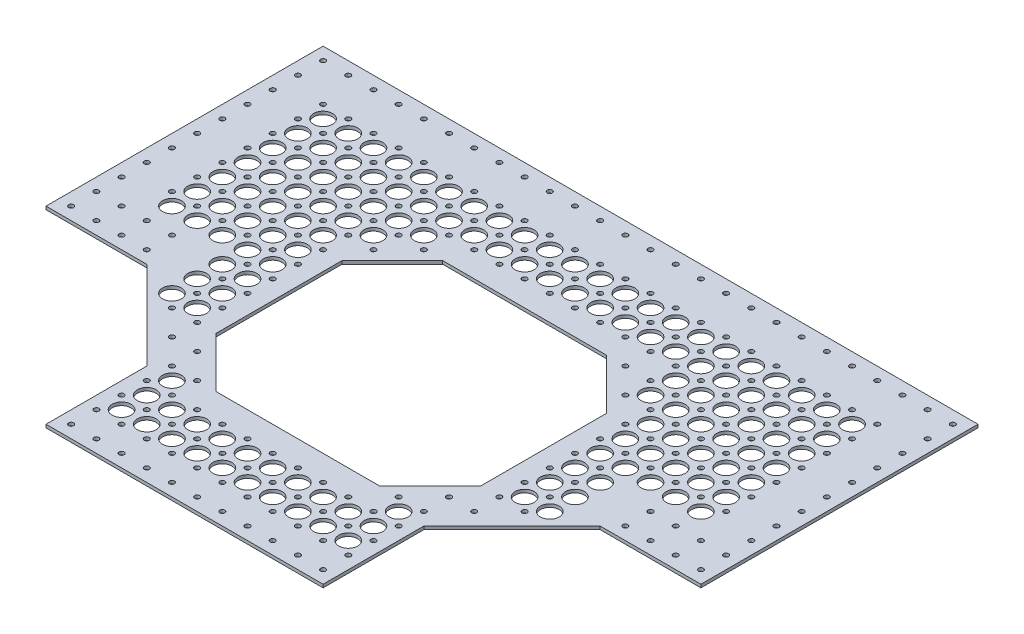
SolidWorks part; units mm, degrees
ref_plane "Front Plane" through (0, 0, 0) normal (0, 0, 1) x (1, 0, 0)
ref_plane "Top Plane" through (0, 0, 0) normal (0, 1, 0) x (1, 0, 0)
ref_plane "Right Plane" through (0, 0, 0) normal (1, 0, 0) x (0, 0, -1)
sketch "Sketch1" plane through (0, 0, 0) normal (0, 1, 0) x (1, 0, 0)
  line L0 (0, 0) -> (0, 101.6)
  line L1 (0, 101.6) -> (279.4, 101.6)
  line L2 (279.4, 101.6) -> (279.4, 0)
  line L3 (279.4, 0) -> (368.3045, -88.9045)
  line L4 (368.3045, -88.9045) -> (469.9045, -88.9045)
  line L5 (469.9045, -88.9045) -> (469.9045, -419.1045)
  line L6 (469.9045, -419.1045) -> (368.3045, -419.1045)
  line L7 (368.3045, -419.1045) -> (279.4, -508.0091)
  line L8 (279.4, -508.0091) -> (279.4, -609.6091)
  line L9 (279.4, -609.6091) -> (0, -609.6091)
  line L10 (0, -609.6091) -> (0, -508.0091)
  line L11 (0, -508.0091) -> (-88.9045, -419.1045)
  line L12 (-88.9045, -419.1045) -> (-190.5045, -419.1045)
  line L13 (-190.5045, -419.1045) -> (-190.5045, -88.9045)
  line L14 (-190.5045, -88.9045) -> (-88.9045, -88.9045)
  line L15 (-88.9045, -88.9045) -> (0, 0)
  line L16 (-190.5045, -88.9045) -> (-177.8045, -88.9045)
  line L17 (-177.8045, -88.9045) -> (-177.8045, -419.1045) construction
  line L18 (-177.8045, -419.1045) -> (-190.5045, -419.1045)
  line L19 (-177.8045, -101.6045) -> (-177.8045, -127.0045) construction
  line L20 (139.7, -898.4) -> (139.7, 49101.6) construction
  line L21 (-966.4523, 88.9) -> (49033.5477, 88.9) construction
  line L22 (12.7, 88.9) -> (38.1, 88.9) construction
  line L23 (-1190.5045, -254.0045) -> (48809.4955, -254.0045) construction
  line L24 (-190.5045, -368.3045) -> (-88.9045, -368.3045) construction
  line L25 (-88.9045, -368.3045) -> (-88.9045, -419.1045) construction
  line L26 (-101.6045, -406.4045) -> (-127.0045, -406.4045) construction
  line L27 (-101.6045, -381.0045) -> (-127.0045, -381.0045) construction
  line L28 (-1102.5698, -114.3045) -> (48897.4302, -114.3045) construction
  line L29 (-1089.6596, -165.1045) -> (48910.3404, -165.1045) construction
  line L30 (-177.8045, -127.0045) -> (-152.4045, -127.0045) construction
  circle A0 centre (-177.8045, -101.6045) radius 2.54
  circle A1 centre (-177.8045, -127.0045) radius 2.54
  circle A2 centre (-177.8045, -152.4045) radius 2.54
  circle A3 centre (-177.8045, -177.8045) radius 2.54
  circle A4 centre (-177.8045, -203.2045) radius 2.54
  circle A5 centre (-177.8045, -228.6045) radius 2.54
  circle A6 centre (-177.8045, -254.0045) radius 2.54
  circle A7 centre (-177.8045, -279.4045) radius 2.54
  circle A8 centre (-177.8045, -304.8045) radius 2.54
  circle A9 centre (-177.8045, -330.2045) radius 2.54
  circle A10 centre (-177.8045, -355.6045) radius 2.54
  circle A11 centre (-177.8045, -381.0045) radius 2.54
  circle A12 centre (-177.8045, -406.4045) radius 2.54
  circle A13 centre (457.2045, -406.4045) radius 2.54
  circle A14 centre (457.2045, -381.0045) radius 2.54
  circle A15 centre (457.2045, -355.6045) radius 2.54
  circle A16 centre (457.2045, -330.2045) radius 2.54
  circle A17 centre (457.2045, -304.8045) radius 2.54
  circle A18 centre (457.2045, -279.4045) radius 2.54
  circle A19 centre (457.2045, -254.0045) radius 2.54
  circle A20 centre (457.2045, -228.6045) radius 2.54
  circle A21 centre (457.2045, -152.4045) radius 2.54
  circle A22 centre (457.2045, -177.8045) radius 2.54
  circle A23 centre (457.2045, -203.2045) radius 2.54
  circle A24 centre (457.2045, -127.0045) radius 2.54
  circle A25 centre (457.2045, -101.6045) radius 2.54
  circle A26 centre (12.7, 88.9) radius 2.54
  circle A27 centre (38.1, 88.9) radius 2.54
  circle A28 centre (63.5, 88.9) radius 2.54
  circle A29 centre (88.9, 88.9) radius 2.54
  circle A30 centre (114.3, 88.9) radius 2.54
  circle A31 centre (139.7, 88.9) radius 2.54
  circle A32 centre (165.1, 88.9) radius 2.54
  circle A33 centre (190.5, 88.9) radius 2.54
  circle A34 centre (215.9, 88.9) radius 2.54
  circle A35 centre (241.3, 88.9) radius 2.54
  circle A36 centre (266.7, 88.9) radius 2.54
  circle A37 centre (266.7, -596.9091) radius 2.54
  circle A38 centre (241.3, -596.9091) radius 2.54
  circle A39 centre (215.9, -596.9091) radius 2.54
  circle A40 centre (190.5, -596.9091) radius 2.54
  circle A41 centre (165.1, -596.9091) radius 2.54
  circle A42 centre (139.7, -596.9091) radius 2.54
  circle A43 centre (114.3, -596.9091) radius 2.54
  circle A44 centre (88.9, -596.9091) radius 2.54
  circle A45 centre (63.5, -596.9091) radius 2.54
  circle A46 centre (38.1, -596.9091) radius 2.54
  circle A47 centre (12.7, -596.9091) radius 2.54
  circle A48 centre (-101.6045, -381.0045) radius 2.54
  circle A49 centre (-101.6045, -406.4045) radius 2.54
  circle A50 centre (381.0045, -406.4045) radius 2.54
  circle A51 centre (381.0045, -381.0045) radius 2.54
  circle A52 centre (-127.0045, -406.4045) radius 2.54
  circle A53 centre (-152.4045, -406.4045) radius 2.54
  circle A54 centre (-127.0045, -381.0045) radius 2.54
  circle A55 centre (-152.4045, -381.0045) radius 2.54
  circle A56 centre (431.8045, -381.0045) radius 2.54
  circle A57 centre (406.4045, -381.0045) radius 2.54
  circle A58 centre (431.8045, -406.4045) radius 2.54
  circle A59 centre (406.4045, -406.4045) radius 2.54
  circle A60 centre (-152.4045, -127.0045) radius 2.54
  circle A61 centre (-152.4045, -152.4045) radius 2.54
  circle A62 centre (-127.0045, -127.0045) radius 2.54
  circle A63 centre (-127.0045, -152.4045) radius 2.54
  circle A64 centre (-101.6045, -127.0045) radius 2.54
  circle A65 centre (-101.6045, -152.4045) radius 2.54
  circle A66 centre (-76.2045, -127.0045) radius 2.54
  circle A67 centre (-76.2045, -152.4045) radius 2.54
  circle A68 centre (-50.8045, -127.0045) radius 2.54
  circle A69 centre (-50.8045, -152.4045) radius 2.54
  circle A70 centre (-25.4045, -127.0045) radius 2.54
  circle A71 centre (-25.4045, -152.4045) radius 2.54
  circle A72 centre (-0.0045, -127.0045) radius 2.54
  circle A73 centre (-0.0045, -152.4045) radius 2.54
  circle A74 centre (25.3955, -127.0045) radius 2.54
  circle A75 centre (25.3955, -152.4045) radius 2.54
  circle A76 centre (50.7955, -127.0045) radius 2.54
  circle A77 centre (50.7955, -152.4045) radius 2.54
  circle A78 centre (76.1955, -127.0045) radius 2.54
  circle A79 centre (76.1955, -152.4045) radius 2.54
  circle A80 centre (101.5955, -127.0045) radius 2.54
  circle A81 centre (101.5955, -152.4045) radius 2.54
  circle A82 centre (126.9955, -127.0045) radius 2.54
  circle A83 centre (126.9955, -152.4045) radius 2.54
  circle A84 centre (152.3955, -127.0045) radius 2.54
  circle A85 centre (152.3955, -152.4045) radius 2.54
  circle A86 centre (177.7955, -127.0045) radius 2.54
  circle A87 centre (177.7955, -152.4045) radius 2.54
  circle A88 centre (203.1955, -127.0045) radius 2.54
  circle A89 centre (203.1955, -152.4045) radius 2.54
  circle A90 centre (228.5955, -127.0045) radius 2.54
  circle A91 centre (228.5955, -152.4045) radius 2.54
  circle A92 centre (253.9955, -127.0045) radius 2.54
  circle A93 centre (253.9955, -152.4045) radius 2.54
  circle A94 centre (279.3955, -127.0045) radius 2.54
  circle A95 centre (279.3955, -152.4045) radius 2.54
  circle A96 centre (304.7955, -127.0045) radius 2.54
  circle A97 centre (304.7955, -152.4045) radius 2.54
  circle A98 centre (330.1955, -127.0045) radius 2.54
  circle A99 centre (330.1955, -152.4045) radius 2.54
  circle A100 centre (355.5955, -127.0045) radius 2.54
  circle A101 centre (355.5955, -152.4045) radius 2.54
  circle A102 centre (380.9955, -127.0045) radius 2.54
  circle A103 centre (380.9955, -152.4045) radius 2.54
  circle A104 centre (406.3955, -127.0045) radius 2.54
  circle A105 centre (406.3955, -152.4045) radius 2.54
  circle A106 centre (431.7955, -127.0045) radius 2.54
  circle A107 centre (431.7955, -152.4045) radius 2.54
  point P50 (139.7, 101.6)
  point P105 (-190.5045, -254.0045)
  dimension "D11" = 5.08
  dimension "D16" = 5.08
  dimension "D21" = 5.08
  dimension "D22" = 5.08
  dimension "D1" = 135
  dimension "D2" = 135
  dimension "D3" = 135
  dimension "D4" = 135
  dimension "D5" = 101.6
  dimension "D6" = 279.4
  dimension "D7" = 330.2
  dimension "D8" = 101.6
  dimension "D9" = 125.73
  dimension "D10" = 12.7
  dimension "D12" = 12.7
  dimension "D13" = 25.4
  dimension "D15" = 12.7
  dimension "D17" = 12.7
  dimension "D18" = 25.4
  dimension "D19" = 101.6
  dimension "D20" = 50.8
  dimension "D23" = 12.7
  dimension "D24" = 12.7
  dimension "D25" = 12.7
  dimension "D26" = 12.7
  dimension "D27" = 25.4
  dimension "D28" = 25.4
  dimension "D29" = 25.4
  dimension "D30" = 50.8
  dimension "D31" = 25.4
  dimension "D14" = 13
extrude "Boss-Extrude1" add sketch "Sketch1" along normal blind 3.175 contours L15 L14 L13 L12 L11 L10 L9 L8 L7 L6 L5 L4 L3 L2 L1 L0 A107 A106 A105 A104 A103 A102 A101 A100 A99 A98 A97 A96 A95 A94 A93 A92 region at (139.7, 0, 254.2329)
sketch "Sketch2" plane through (0, 0, -101.6) normal (0, 0, -1) x (-1, 0, 0)
  line L1 (-510.5355, -12.7) -> (251.4645, -12.7)
  line L2 (-510.5355, -12.7) -> (-510.5355, 12.7)
  line L3 (-510.5355, 12.7) -> (251.4645, 12.7)
  line L4 (251.4645, -12.7) -> (251.4645, 12.7)
  line L5 (-510.5355, -12.7) -> (251.4645, 12.7) construction
  line L6 (-510.5355, 12.7) -> (251.4645, -12.7) construction
  point P0 (-129.5355, 0)
  dimension "D1" = 762
  dimension "D2" = 25.4
extrude "Cut-Extrude1" cut sketch "Sketch2" against normal blind 241.3
sketch "Sketch3" plane through (0, 3.175, 0) normal (0, 1, 0) x (1, 0, 0)
  line L0 (-990.1544, -317.5045) -> (49009.8456, -317.5045) construction
  line L1 (-88.9045, -419.1045) -> (-190.5045, -419.1045) construction
  line L2 (-925.1076, -514.3545) -> (49074.8924, -514.3545) construction
  line L3 (139.7, 330.1887) -> (139.7, -609.6091) construction
  line L12 (6.35, -495.3045) -> (273.05, -495.3045)
  line L13 (279.4, -609.6091) -> (0, -609.6091) construction
  line L14 (0, -609.6091) -> (0, -508.0091) construction
  line L15 (6.35, -495.3045) -> (6.35, -317.5045)
  line L16 (6.35, -317.5045) -> (273.05, -317.5045)
  line L17 (273.05, -495.3045) -> (273.05, -317.5045)
  line L18 (6.35, -495.3045) -> (273.05, -317.5045) construction
  line L19 (6.35, -317.5045) -> (273.05, -495.3045) construction
  point P5 (139.7, -406.4045)
  point P9 (139.7, -139.7102)
  point P19 (139.7, -139.7102)
  dimension "D1" = 101.6
  dimension "D2" = 95.25
  dimension "D3" = 177.8
  dimension "D4" = 266.7
  dimension "D6" = 139.7
extrude "Cut-Extrude2" cut sketch "Sketch3" against normal blind 3.175
sketch "Sketch4" plane through (0, 3.175, 0) normal (0, 1, 0) x (1, 0, 0)
  line L0 (222.25, -495.3045) -> (273.05, -444.5045)
  line L1 (6.35, -495.3045) -> (273.05, -495.3045) construction
  line L2 (273.05, -495.3045) -> (273.05, -317.5045) construction
  line L3 (222.25, -495.3045) -> (273.05, -495.3045)
  line L4 (273.05, -495.3045) -> (273.05, -444.5045)
  line L5 (139.7, 369.2915) -> (139.7, -648.6915) construction
  line L7 (279.4, -508.0091) -> (279.4, -609.6091) construction
  line L8 (6.35, -495.3045) -> (6.35, -444.5045)
  line L9 (57.15, -495.3045) -> (6.35, -495.3045)
  line L10 (57.15, -495.3045) -> (6.35, -444.5045)
  point P10 (139.7, -139.7)
  dimension "D1" = 135
  dimension "D2" = 50.8
  dimension "D3" = 139.7
extrude "Boss-Extrude2" add sketch "Sketch4" against normal blind 3.175
sketch "Sketch7" plane through (0, 3.175, 0) normal (0, 1, 0) x (1, 0, 0)
  line L0 (6.35, -317.5045) -> (57.15, -266.7045)
  line L1 (57.15, -266.7045) -> (222.25, -266.7045)
  line L2 (222.25, -266.7045) -> (273.05, -317.5045)
  line L3 (273.05, -317.5045) -> (6.35, -317.5045) construction
  line L4 (6.35, -317.5045) -> (273.05, -317.5045)
  dimension "D1" = 165.1
  dimension "D2" = 45
  dimension "D3" = 45
extrude "Cut-Extrude3" cut sketch "Sketch7" against normal blind 3.175
sketch "Sketch8" plane through (0, 3.175, 0) normal (0, 1, 0) x (1, 0, 0)
  line L0 (-88.9045, -419.1045) -> (-190.5045, -419.1045) construction
  line L1 (0, -609.6091) -> (0, -508.0091) construction
  line L2 (12.7, -596.9091) -> (12.7, -571.5091) construction
  line L3 (279.4, -508.0091) -> (279.4, -609.6091) construction
  line L4 (76.1955, -533.4) -> (101.5955, -533.4) construction
  line L5 (292.1, -292.1091) -> (292.1, -317.5091) construction
  line L6 (-190.5045, -419.1045) -> (-190.5045, -139.7) construction
  line L7 (-190.5045, -139.7) -> (469.9045, -139.7) construction
  line L8 (-127.0045, -203.2) -> (-101.6045, -203.2) construction
  line L9 (-127.0045, -203.2) -> (-127.0045, -228.6) construction
  line L10 (-25.4045, -381) -> (-50.8045, -381) construction
  line L11 (50.7955, -533.4) -> (25.3955, -533.4) construction
  line L12 (228.5955, -533.4) -> (253.9955, -533.4) construction
  line L13 (25.3955, -533.4) -> (25.3955, -508) construction
  line L14 (253.9955, -533.4) -> (253.9955, -508) construction
  line L15 (330.1955, -431.8) -> (304.7955, -431.8) construction
  line L16 (304.7955, -279.4) -> (279.3955, -279.4) construction
  circle A0 centre (12.7, -596.9091) radius 2.54
  circle A1 centre (12.7, -571.5091) radius 2.54
  circle A2 centre (12.7, -546.1091) radius 2.54
  circle A3 centre (12.7, -520.7091) radius 2.54
  circle A4 centre (12.7, -495.3091) radius 2.54
  circle A5 centre (12.7, -469.9091) radius 2.54
  circle A12 centre (12.7, -292.1091) radius 2.54
  circle A13 centre (12.7, -266.7091) radius 2.54
  circle A14 centre (12.7, -241.3091) radius 2.54
  circle A15 centre (12.7, -215.9091) radius 2.54
  circle A16 centre (12.7, -190.5091) radius 2.54
  circle A19 centre (38.1, -190.5091) radius 2.54
  circle A20 centre (38.1, -215.9091) radius 2.54
  circle A21 centre (38.1, -241.3091) radius 2.54
  circle A22 centre (38.1, -266.7091) radius 2.54
  circle A30 centre (38.1, -495.3091) radius 2.54
  circle A31 centre (38.1, -520.7091) radius 2.54
  circle A32 centre (38.1, -546.1091) radius 2.54
  circle A33 centre (38.1, -571.5091) radius 2.54
  circle A35 centre (63.5, -190.5091) radius 2.54
  circle A36 centre (63.5, -215.9091) radius 2.54
  circle A37 centre (63.5, -241.3091) radius 2.54
  circle A47 centre (63.5, -520.7091) radius 2.54
  circle A48 centre (63.5, -546.1091) radius 2.54
  circle A49 centre (63.5, -571.5091) radius 2.54
  circle A51 centre (88.9, -190.5091) radius 2.54
  circle A52 centre (88.9, -215.9091) radius 2.54
  circle A53 centre (88.9, -241.3091) radius 2.54
  circle A63 centre (88.9, -520.7091) radius 2.54
  circle A64 centre (88.9, -546.1091) radius 2.54
  circle A65 centre (88.9, -571.5091) radius 2.54
  circle A67 centre (114.3, -190.5091) radius 2.54
  circle A68 centre (114.3, -215.9091) radius 2.54
  circle A69 centre (114.3, -241.3091) radius 2.54
  circle A79 centre (114.3, -520.7091) radius 2.54
  circle A80 centre (114.3, -546.1091) radius 2.54
  circle A81 centre (114.3, -571.5091) radius 2.54
  circle A83 centre (139.7, -190.5091) radius 2.54
  circle A84 centre (139.7, -215.9091) radius 2.54
  circle A85 centre (139.7, -241.3091) radius 2.54
  circle A95 centre (139.7, -520.7091) radius 2.54
  circle A96 centre (139.7, -546.1091) radius 2.54
  circle A97 centre (139.7, -571.5091) radius 2.54
  circle A99 centre (165.1, -190.5091) radius 2.54
  circle A100 centre (165.1, -215.9091) radius 2.54
  circle A101 centre (165.1, -241.3091) radius 2.54
  circle A111 centre (165.1, -520.7091) radius 2.54
  circle A112 centre (165.1, -546.1091) radius 2.54
  circle A113 centre (165.1, -571.5091) radius 2.54
  circle A115 centre (190.5, -190.5091) radius 2.54
  circle A116 centre (190.5, -215.9091) radius 2.54
  circle A117 centre (190.5, -241.3091) radius 2.54
  circle A127 centre (190.5, -520.7091) radius 2.54
  circle A128 centre (190.5, -546.1091) radius 2.54
  circle A129 centre (190.5, -571.5091) radius 2.54
  circle A131 centre (215.9, -190.5091) radius 2.54
  circle A132 centre (215.9, -215.9091) radius 2.54
  circle A133 centre (215.9, -241.3091) radius 2.54
  circle A143 centre (215.9, -520.7091) radius 2.54
  circle A144 centre (215.9, -546.1091) radius 2.54
  circle A145 centre (215.9, -571.5091) radius 2.54
  circle A147 centre (241.3, -190.5091) radius 2.54
  circle A148 centre (241.3, -215.9091) radius 2.54
  circle A149 centre (241.3, -241.3091) radius 2.54
  circle A150 centre (241.3, -266.7091) radius 2.54
  circle A158 centre (241.3, -495.3091) radius 2.54
  circle A159 centre (241.3, -520.7091) radius 2.54
  circle A160 centre (241.3, -546.1091) radius 2.54
  circle A161 centre (241.3, -571.5091) radius 2.54
  circle A163 centre (266.7, -190.5091) radius 2.54
  circle A164 centre (266.7, -215.9091) radius 2.54
  circle A165 centre (266.7, -241.3091) radius 2.54
  circle A166 centre (266.7, -266.7091) radius 2.54
  circle A167 centre (266.7, -292.1091) radius 2.54
  circle A173 centre (266.7, -469.9091) radius 2.54
  circle A174 centre (266.7, -495.3091) radius 2.54
  circle A175 centre (266.7, -520.7091) radius 2.54
  circle A176 centre (266.7, -546.1091) radius 2.54
  circle A177 centre (266.7, -571.5091) radius 2.54
  circle A179 centre (292.1, -190.5091) radius 2.54
  circle A180 centre (292.1, -215.9091) radius 2.54
  circle A181 centre (292.1, -241.3091) radius 2.54
  circle A182 centre (292.1, -266.7091) radius 2.54
  circle A183 centre (292.1, -292.1091) radius 2.54
  circle A189 centre (292.1, -469.9091) radius 2.54
  circle A195 centre (317.5, -190.5091) radius 2.54
  circle A196 centre (317.5, -215.9091) radius 2.54
  circle A197 centre (317.5, -241.3091) radius 2.54
  circle A198 centre (317.5, -266.7091) radius 2.54
  circle A199 centre (317.5, -292.1091) radius 2.54
  circle A211 centre (342.9, -190.5091) radius 2.54
  circle A212 centre (342.9, -215.9091) radius 2.54
  circle A213 centre (342.9, -241.3091) radius 2.54
  circle A214 centre (342.9, -266.7091) radius 2.54
  circle A215 centre (342.9, -292.1091) radius 2.54
  circle A227 centre (368.3, -190.5091) radius 2.54
  circle A228 centre (368.3, -215.9091) radius 2.54
  circle A229 centre (368.3, -241.3091) radius 2.54
  circle A230 centre (368.3, -266.7091) radius 2.54
  circle A231 centre (368.3, -292.1091) radius 2.54
  circle A243 centre (393.7, -190.5091) radius 2.54
  circle A244 centre (393.7, -215.9091) radius 2.54
  circle A245 centre (393.7, -241.3091) radius 2.54
  circle A246 centre (393.7, -266.7091) radius 2.54
  circle A247 centre (393.7, -292.1091) radius 2.54
  circle A259 centre (419.1, -190.5091) radius 2.54
  circle A260 centre (419.1, -215.9091) radius 2.54
  circle A261 centre (419.1, -241.3091) radius 2.54
  circle A262 centre (419.1, -266.7091) radius 2.54
  circle A263 centre (419.1, -292.1091) radius 2.54
  circle A291 centre (-12.7, -190.5091) radius 2.54
  circle A292 centre (-12.7, -215.9091) radius 2.54
  circle A293 centre (-12.7, -241.3091) radius 2.54
  circle A294 centre (-12.7, -266.7091) radius 2.54
  circle A295 centre (-12.7, -292.1091) radius 2.54
  circle A302 centre (-12.7, -469.9091) radius 2.54
  circle A308 centre (-38.1, -190.5091) radius 2.54
  circle A309 centre (-38.1, -215.9091) radius 2.54
  circle A310 centre (-38.1, -241.3091) radius 2.54
  circle A311 centre (-38.1, -266.7091) radius 2.54
  circle A312 centre (-38.1, -292.1091) radius 2.54
  circle A325 centre (-63.5, -190.5091) radius 2.54
  circle A326 centre (-63.5, -215.9091) radius 2.54
  circle A327 centre (-63.5, -241.3091) radius 2.54
  circle A328 centre (-63.5, -266.7091) radius 2.54
  circle A329 centre (-63.5, -292.1091) radius 2.54
  circle A342 centre (-88.9, -190.5091) radius 2.54
  circle A343 centre (-88.9, -215.9091) radius 2.54
  circle A344 centre (-88.9, -241.3091) radius 2.54
  circle A345 centre (-88.9, -266.7091) radius 2.54
  circle A346 centre (-88.9, -292.1091) radius 2.54
  circle A359 centre (-114.3, -190.5091) radius 2.54
  circle A360 centre (-114.3, -215.9091) radius 2.54
  circle A361 centre (-114.3, -241.3091) radius 2.54
  circle A362 centre (-114.3, -266.7091) radius 2.54
  circle A363 centre (-114.3, -292.1091) radius 2.54
  circle A376 centre (-139.7, -190.5091) radius 2.54
  circle A377 centre (-139.7, -215.9091) radius 2.54
  circle A378 centre (-139.7, -241.3091) radius 2.54
  circle A379 centre (-139.7, -266.7091) radius 2.54
  circle A380 centre (-139.7, -292.1091) radius 2.54
  circle A409 centre (-63.5, -495.3091) radius 2.54 [skipped]
  circle A410 centre (-63.5, -520.7091) radius 2.54 [skipped]
  circle A411 centre (-63.5, -546.1091) radius 2.54 [skipped]
  circle A412 centre (-63.5, -571.5091) radius 2.54 [skipped]
  circle A413 centre (-88.9, -469.9091) radius 2.54 [skipped]
  circle A414 centre (-88.9, -495.3091) radius 2.54 [skipped]
  circle A415 centre (-88.9, -520.7091) radius 2.54 [skipped]
  circle A416 centre (-88.9, -546.1091) radius 2.54 [skipped]
  circle A417 centre (-88.9, -571.5091) radius 2.54 [skipped]
  circle A418 centre (-114.3, -469.9091) radius 2.54 [skipped]
  circle A419 centre (-114.3, -495.3091) radius 2.54 [skipped]
  circle A420 centre (-114.3, -520.7091) radius 2.54 [skipped]
  circle A421 centre (-114.3, -546.1091) radius 2.54 [skipped]
  circle A422 centre (-114.3, -571.5091) radius 2.54 [skipped]
  circle A423 centre (-139.7, -469.9091) radius 2.54 [skipped]
  circle A424 centre (-139.7, -495.3091) radius 2.54 [skipped]
  circle A425 centre (-139.7, -520.7091) radius 2.54 [skipped]
  circle A426 centre (-139.7, -546.1091) radius 2.54 [skipped]
  circle A427 centre (-139.7, -571.5091) radius 2.54 [skipped]
  circle A428 centre (-165.1, -469.9091) radius 2.54 [skipped]
  circle A429 centre (-165.1, -495.3091) radius 2.54 [skipped]
  circle A430 centre (-165.1, -520.7091) radius 2.54 [skipped]
  circle A431 centre (-165.1, -546.1091) radius 2.54 [skipped]
  circle A432 centre (-165.1, -571.5091) radius 2.54 [skipped]
  circle A433 centre (-63.5, -469.9091) radius 2.54 [skipped]
  circle A434 centre (-12.7, -495.3091) radius 2.54 [skipped]
  circle A435 centre (-12.7, -520.7091) radius 2.54 [skipped]
  circle A436 centre (-12.7, -546.1091) radius 2.54 [skipped]
  circle A437 centre (-12.7, -571.5091) radius 2.54 [skipped]
  circle A438 centre (-38.1, -495.3091) radius 2.54 [skipped]
  circle A439 centre (-38.1, -520.7091) radius 2.54 [skipped]
  circle A440 centre (-38.1, -546.1091) radius 2.54 [skipped]
  circle A441 centre (-38.1, -571.5091) radius 2.54 [skipped]
  circle A442 centre (-127.0045, -203.2) radius 9.525
  circle A443 centre (-101.6045, -203.2) radius 9.525
  circle A444 centre (-76.2045, -203.2) radius 9.525
  circle A445 centre (-50.8045, -203.2) radius 9.525
  circle A446 centre (-25.4045, -203.2) radius 9.525
  circle A447 centre (-0.0045, -203.2) radius 9.525
  circle A448 centre (25.3955, -203.2) radius 9.525
  circle A449 centre (50.7955, -203.2) radius 9.525
  circle A450 centre (76.1955, -203.2) radius 9.525
  circle A451 centre (-38.1, -469.9091) radius 2.54 [skipped]
  circle A452 centre (101.5955, -203.2) radius 9.525
  circle A453 centre (126.9955, -203.2) radius 9.525
  circle A454 centre (152.3955, -203.2) radius 9.525
  circle A455 centre (177.7955, -203.2) radius 9.525
  circle A456 centre (203.1955, -203.2) radius 9.525
  circle A457 centre (228.5955, -203.2) radius 9.525
  circle A458 centre (253.9955, -203.2) radius 9.525
  circle A459 centre (279.3955, -203.2) radius 9.525
  circle A460 centre (304.7955, -203.2) radius 9.525
  circle A461 centre (330.1955, -203.2) radius 9.525
  circle A462 centre (355.5955, -203.2) radius 9.525
  circle A463 centre (380.9955, -203.2) radius 9.525
  circle A464 centre (406.3955, -203.2) radius 9.525
  circle A467 centre (-101.6045, -228.6) radius 9.525
  circle A468 centre (-76.2045, -228.6) radius 9.525
  circle A469 centre (-50.8045, -228.6) radius 9.525
  circle A470 centre (-25.4045, -228.6) radius 9.525
  circle A471 centre (-0.0045, -228.6) radius 9.525
  circle A472 centre (25.3955, -228.6) radius 9.525
  circle A473 centre (50.7955, -228.6) radius 9.525
  circle A474 centre (76.1955, -228.6) radius 9.525
  circle A475 centre (101.5955, -228.6) radius 9.525
  circle A476 centre (126.9955, -228.6) radius 9.525
  circle A477 centre (152.3955, -228.6) radius 9.525
  circle A478 centre (177.7955, -228.6) radius 9.525
  circle A479 centre (203.1955, -228.6) radius 9.525
  circle A480 centre (228.5955, -228.6) radius 9.525
  circle A481 centre (253.9955, -228.6) radius 9.525
  circle A482 centre (279.3955, -228.6) radius 9.525
  circle A483 centre (304.7955, -228.6) radius 9.525
  circle A484 centre (330.1955, -228.6) radius 9.525
  circle A485 centre (355.5955, -228.6) radius 9.525
  circle A486 centre (380.9955, -228.6) radius 9.525
  circle A487 centre (406.3955, -228.6) radius 9.525
  circle A490 centre (-101.6045, -254) radius 9.525
  circle A491 centre (-76.2045, -254) radius 9.525
  circle A492 centre (-50.8045, -254) radius 9.525
  circle A493 centre (-25.4045, -254) radius 9.525
  circle A494 centre (-0.0045, -254) radius 9.525
  circle A495 centre (25.3955, -254) radius 9.525
  circle A497 centre (38.1, -292.1091) radius 2.54 [skipped]
  circle A498 centre (63.5, -292.1091) radius 2.54 [skipped]
  circle A499 centre (88.9, -292.1091) radius 2.54 [skipped]
  circle A500 centre (114.3, -292.1091) radius 2.54 [skipped]
  circle A501 centre (139.7, -292.1091) radius 2.54 [skipped]
  circle A502 centre (165.1, -292.1091) radius 2.54 [skipped]
  circle A503 centre (190.5, -292.1091) radius 2.54 [skipped]
  circle A504 centre (241.3, -292.1091) radius 2.54 [skipped]
  circle A505 centre (215.9, -292.1091) radius 2.54 [skipped]
  circle A506 centre (63.5, -266.7091) radius 2.54 [skipped]
  circle A507 centre (88.9, -266.7091) radius 2.54 [skipped]
  circle A508 centre (114.3, -266.7091) radius 2.54 [skipped]
  circle A509 centre (139.7, -266.7091) radius 2.54 [skipped]
  circle A510 centre (165.1, -266.7091) radius 2.54 [skipped]
  circle A511 centre (215.9, -266.7091) radius 2.54 [skipped]
  circle A512 centre (190.5, -266.7091) radius 2.54 [skipped]
  circle A518 centre (12.7, -419.1091) radius 2.54 [skipped]
  circle A519 centre (12.7, -393.7091) radius 2.54 [skipped]
  circle A520 centre (12.7, -368.3091) radius 2.54 [skipped]
  circle A521 centre (12.7, -342.9091) radius 2.54 [skipped]
  circle A522 centre (12.7, -317.5091) radius 2.54 [skipped]
  circle A523 centre (12.7, -444.5091) radius 2.54 [skipped]
  circle A524 centre (292.1, -546.1091) radius 2.54 [skipped]
  circle A525 centre (292.1, -571.5091) radius 2.54 [skipped]
  circle A526 centre (317.5, -520.7091) radius 2.54 [skipped]
  circle A527 centre (317.5, -546.1091) radius 2.54 [skipped]
  circle A528 centre (317.5, -571.5091) radius 2.54 [skipped]
  circle A529 centre (342.9, -520.7091) radius 2.54 [skipped]
  circle A530 centre (342.9, -546.1091) radius 2.54 [skipped]
  circle A531 centre (342.9, -571.5091) radius 2.54 [skipped]
  circle A532 centre (368.3, -520.7091) radius 2.54 [skipped]
  circle A533 centre (368.3, -546.1091) radius 2.54 [skipped]
  circle A534 centre (368.3, -571.5091) radius 2.54 [skipped]
  circle A535 centre (393.7, -520.7091) radius 2.54 [skipped]
  circle A536 centre (393.7, -546.1091) radius 2.54 [skipped]
  circle A537 centre (393.7, -571.5091) radius 2.54 [skipped]
  circle A538 centre (419.1, -520.7091) radius 2.54 [skipped]
  circle A539 centre (419.1, -546.1091) radius 2.54 [skipped]
  circle A540 centre (419.1, -571.5091) radius 2.54 [skipped]
  circle A541 centre (444.5, -520.7091) radius 2.54 [skipped]
  circle A542 centre (444.5, -546.1091) radius 2.54 [skipped]
  circle A543 centre (444.5, -571.5091) radius 2.54 [skipped]
  circle A544 centre (292.1, -520.7091) radius 2.54 [skipped]
  circle A545 centre (317.5, -495.3091) radius 2.54 [skipped]
  circle A546 centre (342.9, -495.3091) radius 2.54 [skipped]
  circle A547 centre (368.3, -495.3091) radius 2.54 [skipped]
  circle A548 centre (393.7, -495.3091) radius 2.54 [skipped]
  circle A549 centre (419.1, -495.3091) radius 2.54 [skipped]
  circle A550 centre (444.5, -495.3091) radius 2.54 [skipped]
  circle A551 centre (292.1, -495.3091) radius 2.54 [skipped]
  circle A552 centre (317.5, -469.9091) radius 2.54 [skipped]
  circle A553 centre (342.9, -469.9091) radius 2.54 [skipped]
  circle A554 centre (368.3, -469.9091) radius 2.54 [skipped]
  circle A555 centre (393.7, -469.9091) radius 2.54 [skipped]
  circle A556 centre (419.1, -469.9091) radius 2.54 [skipped]
  circle A557 centre (444.5, -469.9091) radius 2.54 [skipped]
  circle A558 centre (38.1, -469.9091) radius 2.54 [skipped]
  circle A559 centre (63.5, -469.9091) radius 2.54 [skipped]
  circle A560 centre (88.9, -469.9091) radius 2.54 [skipped]
  circle A561 centre (114.3, -469.9091) radius 2.54 [skipped]
  circle A562 centre (139.7, -469.9091) radius 2.54 [skipped]
  circle A563 centre (165.1, -469.9091) radius 2.54 [skipped]
  circle A564 centre (190.5, -469.9091) radius 2.54 [skipped]
  circle A565 centre (215.9, -469.9091) radius 2.54 [skipped]
  circle A566 centre (241.3, -469.9091) radius 2.54 [skipped]
  circle A567 centre (63.5, -495.3091) radius 2.54 [skipped]
  circle A568 centre (88.9, -495.3091) radius 2.54 [skipped]
  circle A569 centre (114.3, -495.3091) radius 2.54 [skipped]
  circle A570 centre (139.7, -495.3091) radius 2.54 [skipped]
  circle A571 centre (165.1, -495.3091) radius 2.54 [skipped]
  circle A572 centre (190.5, -495.3091) radius 2.54 [skipped]
  circle A573 centre (215.9, -495.3091) radius 2.54 [skipped]
  circle A575 centre (-139.7, -317.5091) radius 2.54
  circle A576 centre (-114.3, -317.5091) radius 2.54
  circle A577 centre (-88.9, -317.5091) radius 2.54
  circle A578 centre (-63.5, -317.5091) radius 2.54
  circle A579 centre (-38.1, -317.5091) radius 2.54
  circle A580 centre (-12.7, -317.5091) radius 2.54
  circle A582 centre (-139.7, -342.9091) radius 2.54
  circle A583 centre (-114.3, -342.9091) radius 2.54
  circle A584 centre (-88.9, -342.9091) radius 2.54
  circle A585 centre (-63.5, -342.9091) radius 2.54
  circle A586 centre (-38.1, -342.9091) radius 2.54
  circle A587 centre (-12.7, -342.9091) radius 2.54
  circle A593 centre (-38.1, -368.3091) radius 2.54
  circle A594 centre (-12.7, -368.3091) radius 2.54
  circle A600 centre (-38.1, -393.7091) radius 2.54
  circle A601 centre (-12.7, -393.7091) radius 2.54
  circle A607 centre (-38.1, -419.1091) radius 2.54
  circle A608 centre (-12.7, -419.1091) radius 2.54
  circle A614 centre (-38.1, -444.5091) radius 2.54
  circle A615 centre (-12.7, -444.5091) radius 2.54
  circle A616 centre (292.1, -317.5091) radius 2.54
  circle A617 centre (317.5, -317.5091) radius 2.54
  circle A618 centre (342.9, -317.5091) radius 2.54
  circle A619 centre (368.3, -317.5091) radius 2.54
  circle A620 centre (393.7, -317.5091) radius 2.54
  circle A621 centre (419.1, -317.5091) radius 2.54
  circle A623 centre (292.1, -342.9091) radius 2.54
  circle A624 centre (317.5, -342.9091) radius 2.54
  circle A625 centre (342.9, -342.9091) radius 2.54
  circle A626 centre (368.3, -342.9091) radius 2.54
  circle A627 centre (393.7, -342.9091) radius 2.54
  circle A628 centre (419.1, -342.9091) radius 2.54
  circle A630 centre (292.1, -368.3091) radius 2.54
  circle A631 centre (317.5, -368.3091) radius 2.54
  circle A637 centre (292.1, -393.7091) radius 2.54
  circle A638 centre (317.5, -393.7091) radius 2.54
  circle A644 centre (292.1, -419.1091) radius 2.54
  circle A645 centre (317.5, -419.1091) radius 2.54
  circle A651 centre (292.1, -444.5091) radius 2.54
  circle A652 centre (317.5, -444.5091) radius 2.54
  circle A658 centre (342.9, -444.5091) radius 2.54 [skipped]
  circle A659 centre (393.7, -444.5091) radius 2.54 [skipped]
  circle A660 centre (419.1, -444.5091) radius 2.54 [skipped]
  circle A661 centre (101.5955, -533.4) radius 9.525
  circle A662 centre (368.3, -444.5091) radius 2.54 [skipped]
  circle A663 centre (393.7, -419.1091) radius 2.54 [skipped]
  circle A664 centre (419.1, -419.1091) radius 2.54 [skipped]
  circle A665 centre (126.9955, -533.4) radius 9.525
  circle A666 centre (368.3, -419.1091) radius 2.54 [skipped]
  circle A667 centre (393.7, -393.7091) radius 2.54 [skipped]
  circle A668 centre (419.1, -393.7091) radius 2.54 [skipped]
  circle A669 centre (152.3955, -533.4) radius 9.525
  circle A670 centre (177.7955, -533.4) radius 9.525
  circle A671 centre (-139.7, -444.5091) radius 2.54 [skipped]
  circle A672 centre (-114.3, -444.5091) radius 2.54 [skipped]
  circle A673 centre (-63.5, -444.5091) radius 2.54 [skipped]
  circle A674 centre (-88.9, -444.5091) radius 2.54 [skipped]
  circle A675 centre (203.1955, -533.4) radius 9.525
  circle A676 centre (-139.7, -393.7091) radius 2.54 [skipped]
  circle A677 centre (-114.3, -393.7091) radius 2.54 [skipped]
  circle A678 centre (228.5955, -533.4) radius 9.525
  circle A679 centre (-139.7, -419.1091) radius 2.54 [skipped]
  circle A680 centre (-114.3, -419.1091) radius 2.54 [skipped]
  circle A681 centre (-88.9, -419.1091) radius 2.54 [skipped]
  circle A685 centre (279.3955, -254) radius 9.525
  circle A686 centre (304.7955, -254) radius 9.525
  circle A687 centre (330.1955, -254) radius 9.525
  circle A688 centre (355.5955, -254) radius 9.525
  circle A689 centre (380.9955, -254) radius 9.525
  circle A690 centre (406.3955, -254) radius 9.525
  circle A693 centre (-101.6045, -279.4) radius 9.525
  circle A694 centre (-76.2045, -279.4) radius 9.525
  circle A695 centre (-50.8045, -279.4) radius 9.525
  circle A696 centre (-25.4045, -279.4) radius 9.525
  circle A697 centre (-0.0045, -279.4) radius 9.525
  circle A709 centre (304.7955, -279.4) radius 9.525
  circle A710 centre (330.1955, -279.4) radius 9.525
  circle A711 centre (355.5955, -279.4) radius 9.525
  circle A712 centre (380.9955, -279.4) radius 9.525
  circle A713 centre (406.3955, -279.4) radius 9.525
  circle A716 centre (-101.6045, -304.8) radius 9.525
  circle A717 centre (-76.2045, -304.8) radius 9.525
  circle A718 centre (-50.8045, -304.8) radius 9.525
  circle A719 centre (-25.4045, -304.8) radius 9.525
  circle A723 centre (76.1955, -304.8) radius 9.525 [skipped]
  circle A724 centre (101.5955, -304.8) radius 9.525 [skipped]
  circle A725 centre (126.9955, -304.8) radius 9.525 [skipped]
  circle A726 centre (152.3955, -304.8) radius 9.525 [skipped]
  circle A727 centre (177.7955, -304.8) radius 9.525 [skipped]
  circle A728 centre (203.1955, -304.8) radius 9.525 [skipped]
  circle A729 centre (228.5955, -304.8) radius 9.525 [skipped]
  circle A730 centre (253.9955, -304.8) radius 9.525 [skipped]
  circle A733 centre (330.1955, -304.8) radius 9.525
  circle A734 centre (355.5955, -304.8) radius 9.525
  circle A735 centre (380.9955, -304.8) radius 9.525
  circle A736 centre (406.3955, -304.8) radius 9.525
  circle A739 centre (-101.6045, -330.2) radius 9.525
  circle A740 centre (-76.2045, -330.2) radius 9.525
  circle A741 centre (-50.8045, -330.2) radius 9.525
  circle A742 centre (-25.4045, -330.2) radius 9.525
  circle A745 centre (50.7955, -330.2) radius 9.525 [skipped]
  circle A746 centre (76.1955, -330.2) radius 9.525 [skipped]
  circle A747 centre (101.5955, -330.2) radius 9.525 [skipped]
  circle A748 centre (126.9955, -330.2) radius 9.525 [skipped]
  circle A749 centre (152.3955, -330.2) radius 9.525 [skipped]
  circle A750 centre (177.7955, -330.2) radius 9.525 [skipped]
  circle A751 centre (203.1955, -330.2) radius 9.525 [skipped]
  circle A752 centre (228.5955, -330.2) radius 9.525 [skipped]
  circle A753 centre (253.9955, -330.2) radius 9.525 [skipped]
  circle A754 centre (279.3955, -330.2) radius 9.525 [skipped]
  circle A756 centre (330.1955, -330.2) radius 9.525
  circle A757 centre (355.5955, -330.2) radius 9.525
  circle A758 centre (380.9955, -330.2) radius 9.525
  circle A759 centre (406.3955, -330.2) radius 9.525
  circle A762 centre (-101.6045, -355.6) radius 9.525
  circle A763 centre (-76.2045, -355.6) radius 9.525
  circle A764 centre (-50.8045, -355.6) radius 9.525
  circle A765 centre (-25.4045, -355.6) radius 9.525
  circle A768 centre (50.7955, -355.6) radius 9.525 [skipped]
  circle A769 centre (76.1955, -355.6) radius 9.525 [skipped]
  circle A770 centre (101.5955, -355.6) radius 9.525 [skipped]
  circle A771 centre (126.9955, -355.6) radius 9.525 [skipped]
  circle A772 centre (152.3955, -355.6) radius 9.525 [skipped]
  circle A773 centre (177.7955, -355.6) radius 9.525 [skipped]
  circle A774 centre (203.1955, -355.6) radius 9.525 [skipped]
  circle A775 centre (228.5955, -355.6) radius 9.525 [skipped]
  circle A776 centre (253.9955, -355.6) radius 9.525 [skipped]
  circle A777 centre (279.3955, -355.6) radius 9.525 [skipped]
  circle A779 centre (330.1955, -355.6) radius 9.525
  circle A780 centre (355.5955, -355.6) radius 9.525
  circle A781 centre (380.9955, -355.6) radius 9.525
  circle A782 centre (406.3955, -355.6) radius 9.525
  circle A788 centre (-25.4045, -381) radius 9.525
  circle A791 centre (50.7955, -381) radius 9.525 [skipped]
  circle A792 centre (76.1955, -381) radius 9.525 [skipped]
  circle A799 centre (253.9955, -381) radius 9.525 [skipped]
  circle A800 centre (279.3955, -381) radius 9.525 [skipped]
  circle A802 centre (330.1955, -381) radius 9.525
  circle A811 centre (-25.4045, -406.4) radius 9.525
  circle A814 centre (50.7955, -406.4) radius 9.525 [skipped]
  circle A815 centre (76.1955, -406.4) radius 9.525 [skipped]
  circle A825 centre (330.1955, -406.4) radius 9.525
  circle A834 centre (-25.4045, -431.8) radius 9.525
  circle A837 centre (50.7955, -431.8) radius 9.525 [skipped]
  circle A838 centre (76.1955, -431.8) radius 9.525 [skipped]
  circle A848 centre (330.1955, -431.8) radius 9.525
  circle A856 centre (-50.8045, -457.2) radius 9.525 [skipped]
  circle A860 centre (50.7955, -457.2) radius 9.525 [skipped]
  circle A861 centre (76.1955, -457.2) radius 9.525 [skipped]
  circle A873 centre (380.9955, -457.2) radius 9.525 [skipped]
  circle A880 centre (-25.4045, -482.6) radius 9.525 [skipped]
  circle A883 centre (50.7955, -482.6) radius 9.525 [skipped]
  circle A884 centre (76.1955, -482.6) radius 9.525 [skipped]
  circle A892 centre (279.3955, -482.6) radius 9.525 [skipped]
  circle A895 centre (355.5955, -482.6) radius 9.525 [skipped]
  circle A904 centre (-0.0045, -508) radius 9.525 [skipped]
  circle A914 centre (253.9955, -508) radius 9.525 [skipped]
  circle A917 centre (330.1955, -508) radius 9.525 [skipped]
  circle A928 centre (25.3955, -533.4) radius 9.525 [skipped]
  circle A929 centre (50.7955, -533.4) radius 9.525
  circle A930 centre (76.1955, -533.4) radius 9.525
  circle A939 centre (304.7955, -533.4) radius 9.525 [skipped]
  circle A951 centre (25.3955, -558.8) radius 9.525 [skipped]
  circle A952 centre (50.7955, -558.8) radius 9.525
  circle A953 centre (76.1955, -558.8) radius 9.525
  circle A954 centre (101.5955, -558.8) radius 9.525
  circle A955 centre (126.9955, -558.8) radius 9.525
  circle A956 centre (152.3955, -558.8) radius 9.525
  circle A957 centre (177.7955, -558.8) radius 9.525
  circle A958 centre (203.1955, -558.8) radius 9.525
  circle A959 centre (228.5955, -558.8) radius 9.525
  circle A962 centre (304.7955, -558.8) radius 9.525 [skipped]
  circle A985 centre (-50.8045, -381) radius 9.525
  circle A992 centre (-127.0045, -228.6) radius 9.525
  circle A993 centre (-127.0045, -254) radius 9.525
  circle A994 centre (-127.0045, -279.4) radius 9.525
  circle A995 centre (-127.0045, -304.8) radius 9.525
  circle A996 centre (-127.0045, -330.2) radius 9.525
  circle A997 centre (-127.0045, -355.6) radius 9.525
  circle A1007 centre (76.1955, -508) radius 9.525 [skipped]
  circle A1008 centre (25.3955, -355.6) radius 9.525 [skipped]
  circle A1009 centre (25.3955, -381) radius 9.525 [skipped]
  circle A1010 centre (25.3955, -406.4) radius 9.525 [skipped]
  circle A1011 centre (25.3955, -431.8) radius 9.525 [skipped]
  circle A1012 centre (25.3955, -457.2) radius 9.525 [skipped]
  circle A1013 centre (279.3955, -457.2) radius 9.525 [skipped]
  circle A1014 centre (101.5955, -381) radius 9.525 [skipped]
  circle A1015 centre (126.9955, -381) radius 9.525 [skipped]
  circle A1016 centre (152.3955, -381) radius 9.525 [skipped]
  circle A1017 centre (177.7955, -381) radius 9.525 [skipped]
  circle A1018 centre (203.1955, -381) radius 9.525 [skipped]
  circle A1019 centre (228.5955, -381) radius 9.525 [skipped]
  circle A1020 centre (101.5955, -406.4) radius 9.525 [skipped]
  circle A1021 centre (126.9955, -406.4) radius 9.525 [skipped]
  circle A1022 centre (152.3955, -406.4) radius 9.525 [skipped]
  circle A1023 centre (177.7955, -406.4) radius 9.525 [skipped]
  circle A1024 centre (203.1955, -406.4) radius 9.525 [skipped]
  circle A1025 centre (228.5955, -406.4) radius 9.525 [skipped]
  circle A1026 centre (101.5955, -431.8) radius 9.525 [skipped]
  circle A1027 centre (126.9955, -431.8) radius 9.525 [skipped]
  circle A1028 centre (152.3955, -431.8) radius 9.525 [skipped]
  circle A1029 centre (177.7955, -431.8) radius 9.525 [skipped]
  circle A1030 centre (203.1955, -431.8) radius 9.525 [skipped]
  circle A1031 centre (228.5955, -431.8) radius 9.525 [skipped]
  circle A1032 centre (101.5955, -457.2) radius 9.525 [skipped]
  circle A1033 centre (126.9955, -457.2) radius 9.525 [skipped]
  circle A1034 centre (152.3955, -457.2) radius 9.525 [skipped]
  circle A1035 centre (177.7955, -457.2) radius 9.525 [skipped]
  circle A1036 centre (203.1955, -457.2) radius 9.525 [skipped]
  circle A1037 centre (228.5955, -457.2) radius 9.525 [skipped]
  circle A1038 centre (101.5955, -482.6) radius 9.525 [skipped]
  circle A1039 centre (126.9955, -482.6) radius 9.525 [skipped]
  circle A1040 centre (152.3955, -482.6) radius 9.525 [skipped]
  circle A1041 centre (177.7955, -482.6) radius 9.525 [skipped]
  circle A1042 centre (203.1955, -482.6) radius 9.525 [skipped]
  circle A1043 centre (228.5955, -482.6) radius 9.525 [skipped]
  circle A1044 centre (101.5955, -508) radius 9.525 [skipped]
  circle A1045 centre (126.9955, -508) radius 9.525 [skipped]
  circle A1046 centre (152.3955, -508) radius 9.525 [skipped]
  circle A1047 centre (177.7955, -508) radius 9.525 [skipped]
  circle A1048 centre (203.1955, -508) radius 9.525 [skipped]
  circle A1049 centre (228.5955, -508) radius 9.525 [skipped]
  circle A1050 centre (253.9955, -406.4) radius 9.525 [skipped]
  circle A1051 centre (279.3955, -406.4) radius 9.525 [skipped]
  circle A1052 centre (253.9955, -431.8) radius 9.525 [skipped]
  circle A1053 centre (253.9955, -457.2) radius 9.525 [skipped]
  circle A1054 centre (279.3955, -431.8) radius 9.525 [skipped]
  circle A1055 centre (253.9955, -482.6) radius 9.525 [skipped]
  circle A1056 centre (304.7955, -355.6) radius 9.525 [skipped]
  circle A1057 centre (304.7955, -381) radius 9.525 [skipped]
  circle A1058 centre (304.7955, -406.4) radius 9.525 [skipped]
  circle A1059 centre (304.7955, -431.8) radius 9.525 [skipped]
  circle A1060 centre (304.7955, -457.2) radius 9.525 [skipped]
  circle A1061 centre (-127.0045, -406.4) radius 9.525 [skipped]
  circle A1062 centre (-101.6045, -406.4) radius 9.525 [skipped]
  circle A1063 centre (-76.2045, -406.4) radius 9.525 [skipped]
  circle A1064 centre (-76.2045, -431.8) radius 9.525 [skipped]
  circle A1065 centre (-101.6045, -431.8) radius 9.525 [skipped]
  circle A1066 centre (-127.0045, -431.8) radius 9.525 [skipped]
  circle A1067 centre (-50.8045, -406.4) radius 9.525
  circle A1068 centre (-139.7, -368.3091) radius 2.54 [skipped]
  circle A1069 centre (-114.3, -368.3091) radius 2.54 [skipped]
  circle A1070 centre (-88.9, -368.3091) radius 2.54 [skipped]
  circle A1071 centre (-88.9, -393.7091) radius 2.54 [skipped]
  circle A1072 centre (-101.6045, -457.2) radius 9.525 [skipped]
  circle A1073 centre (-76.2045, -457.2) radius 9.525 [skipped]
  circle A1074 centre (-101.6045, -482.6) radius 9.525 [skipped]
  circle A1075 centre (-76.2045, -482.6) radius 9.525 [skipped]
  circle A1076 centre (-127.0045, -457.2) radius 9.525 [skipped]
  circle A1077 centre (-127.0045, -482.6) radius 9.525 [skipped]
  circle A1078 centre (-50.8045, -482.6) radius 9.525 [skipped]
  circle A1079 centre (-101.6045, -533.4) radius 9.525 [skipped]
  circle A1080 centre (-76.2045, -533.4) radius 9.525 [skipped]
  circle A1081 centre (-50.8045, -533.4) radius 9.525 [skipped]
  circle A1082 centre (-25.4045, -533.4) radius 9.525 [skipped]
  circle A1083 centre (-0.0045, -533.4) radius 9.525 [skipped]
  circle A1084 centre (-101.6045, -558.8) radius 9.525 [skipped]
  circle A1085 centre (-76.2045, -558.8) radius 9.525 [skipped]
  circle A1086 centre (-50.8045, -558.8) radius 9.525 [skipped]
  circle A1087 centre (-25.4045, -558.8) radius 9.525 [skipped]
  circle A1088 centre (-0.0045, -558.8) radius 9.525 [skipped]
  circle A1089 centre (-50.8045, -431.8) radius 9.525
  circle A1090 centre (25.3955, -533.4) radius 9.525
  circle A1091 centre (25.3955, -558.8) radius 9.525
  circle A1092 centre (253.9955, -533.4) radius 9.525
  circle A1093 centre (-127.0045, -533.4) radius 9.525 [skipped]
  circle A1094 centre (-127.0045, -558.8) radius 9.525 [skipped]
  circle A1095 centre (253.9955, -558.8) radius 9.525
  circle A1096 centre (25.3955, -508) radius 9.525
  circle A1097 centre (-101.6045, -508) radius 9.525 [skipped]
  circle A1098 centre (-76.2045, -508) radius 9.525 [skipped]
  circle A1099 centre (-50.8045, -508) radius 9.525 [skipped]
  circle A1100 centre (-25.4045, -508) radius 9.525 [skipped]
  circle A1101 centre (-127.0045, -508) radius 9.525 [skipped]
  circle A1102 centre (355.5955, -533.4) radius 9.525 [skipped]
  circle A1103 centre (380.9955, -533.4) radius 9.525 [skipped]
  circle A1104 centre (406.3955, -533.4) radius 9.525 [skipped]
  circle A1105 centre (253.9955, -508) radius 9.525
  circle A1106 centre (304.7955, -431.8) radius 9.525
  circle A1107 centre (330.1955, -558.8) radius 9.525 [skipped]
  circle A1108 centre (355.5955, -558.8) radius 9.525 [skipped]
  circle A1109 centre (380.9955, -558.8) radius 9.525 [skipped]
  circle A1110 centre (406.3955, -558.8) radius 9.525 [skipped]
  circle A1111 centre (304.7955, -406.4) radius 9.525
  circle A1112 centre (304.7955, -381) radius 9.525
  circle A1113 centre (304.7955, -355.6) radius 9.525
  circle A1114 centre (304.7955, -330.2) radius 9.525
  circle A1115 centre (304.7955, -304.8) radius 9.525
  circle A1116 centre (279.3955, -279.4) radius 9.525
  circle A1119 centre (330.1955, -533.4) radius 9.525 [skipped]
  circle A1120 centre (380.9955, -508) radius 9.525 [skipped]
  circle A1121 centre (406.3955, -508) radius 9.525 [skipped]
  circle A1124 centre (355.5955, -508) radius 9.525 [skipped]
  circle A1126 centre (380.9955, -482.6) radius 9.525 [skipped]
  circle A1127 centre (406.3955, -482.6) radius 9.525 [skipped]
  circle A1129 centre (406.3955, -457.2) radius 9.525 [skipped]
  circle A1132 centre (406.3955, -431.8) radius 9.525 [skipped]
  circle A1135 centre (406.3955, -406.4) radius 9.525 [skipped]
  circle A1138 centre (368.3, -368.3091) radius 2.54 [skipped]
  circle A1139 centre (368.3, -393.7091) radius 2.54 [skipped]
  circle A1140 centre (393.7, -368.3091) radius 2.54 [skipped]
  circle A1141 centre (419.1, -368.3091) radius 2.54 [skipped]
  circle A1143 centre (380.9955, -406.4) radius 9.525 [skipped]
  circle A1144 centre (380.9955, -431.8) radius 9.525 [skipped]
  circle A1145 centre (342.9, -368.3091) radius 2.54 [skipped]
  circle A1146 centre (342.9, -393.7091) radius 2.54 [skipped]
  circle A1147 centre (342.9, -419.1091) radius 2.54 [skipped]
  circle A1148 centre (-50.8045, -406.4) radius 9.525 [skipped]
  circle A1149 centre (-50.8045, -431.8) radius 9.525 [skipped]
  circle A1150 centre (-63.5, -419.1091) radius 2.54 [skipped]
  circle A1151 centre (-63.5, -393.7091) radius 2.54 [skipped]
  circle A1152 centre (-63.5, -368.3091) radius 2.54 [skipped]
  circle A1177 centre (12.7, -165.1091) radius 2.54 [skipped]
  circle A1178 centre (-165.1, -215.9091) radius 2.54 [skipped]
  circle A1179 centre (-165.1, -241.3091) radius 2.54 [skipped]
  circle A1180 centre (-165.1, -266.7091) radius 2.54 [skipped]
  circle A1181 centre (-165.1, -292.1091) radius 2.54 [skipped]
  circle A1182 centre (-165.1, -190.5091) radius 2.54 [skipped]
  circle A1183 centre (444.5, -215.9091) radius 2.54 [skipped]
  circle A1184 centre (444.5, -241.3091) radius 2.54 [skipped]
  circle A1185 centre (444.5, -266.7091) radius 2.54 [skipped]
  circle A1186 centre (444.5, -292.1091) radius 2.54 [skipped]
  circle A1187 centre (444.5, -190.5091) radius 2.54 [skipped]
  circle A1188 centre (25.3955, -330.2) radius 9.525 [skipped]
  circle A1189 centre (50.7955, -304.8) radius 9.525 [skipped]
  circle A1190 centre (101.5955, -279.4) radius 9.525 [skipped]
  circle A1191 centre (126.9955, -279.4) radius 9.525 [skipped]
  circle A1192 centre (152.3955, -279.4) radius 9.525 [skipped]
  circle A1193 centre (177.7955, -279.4) radius 9.525 [skipped]
  circle A1194 centre (203.1955, -279.4) radius 9.525 [skipped]
  circle A1195 centre (228.5955, -279.4) radius 9.525 [skipped]
  circle A1196 centre (76.1955, -279.4) radius 9.525 [skipped]
  circle A1197 centre (253.9955, -279.4) radius 9.525 [skipped]
  circle A1198 centre (279.3955, -304.8) radius 9.525 [skipped]
  circle A1199 centre (304.7955, -330.2) radius 9.525 [skipped]
  circle A1200 centre (101.5955, -533.4) radius 9.525 [skipped]
  circle A1201 centre (126.9955, -533.4) radius 9.525 [skipped]
  circle A1202 centre (152.3955, -533.4) radius 9.525 [skipped]
  circle A1203 centre (203.1955, -533.4) radius 9.525 [skipped]
  circle A1204 centre (228.5955, -533.4) radius 9.525 [skipped]
  circle A1205 centre (253.9955, -533.4) radius 9.525 [skipped]
  circle A1206 centre (177.7955, -533.4) radius 9.525 [skipped]
  circle A1207 centre (279.3955, -508) radius 9.525 [skipped]
  circle A1208 centre (304.7955, -482.6) radius 9.525 [skipped]
  circle A1209 centre (50.7955, -508) radius 9.525 [skipped]
  circle A1210 centre (25.3955, -482.6) radius 9.525 [skipped]
  circle A1211 centre (-25.4045, -457.2) radius 9.525 [skipped]
  circle A1212 centre (-0.0045, -482.6) radius 9.525 [skipped]
  circle A1213 centre (25.3955, -508) radius 9.525 [skipped]
  circle A1214 centre (-127.0045, -381) radius 9.525 [skipped]
  circle A1215 centre (-76.2045, -381) radius 9.525 [skipped]
  circle A1216 centre (-101.6045, -381) radius 9.525 [skipped]
  circle A1217 centre (406.3955, -381) radius 9.525 [skipped]
  circle A1220 centre (380.9955, -381) radius 9.525 [skipped]
  circle A1221 centre (-50.8045, -381) radius 9.525 [skipped]
  circle A1222 centre (25.3955, -304.8) radius 9.525 [skipped]
  circle A1223 centre (50.7955, -279.4) radius 9.525 [skipped]
  circle A1224 centre (101.5955, -254) radius 9.525 [skipped]
  circle A1225 centre (126.9955, -254) radius 9.525 [skipped]
  circle A1226 centre (152.3955, -254) radius 9.525 [skipped]
  circle A1227 centre (177.7955, -254) radius 9.525 [skipped]
  circle A1228 centre (203.1955, -254) radius 9.525 [skipped]
  circle A1229 centre (228.5955, -254) radius 9.525 [skipped]
  circle A1230 centre (253.9955, -254) radius 9.525 [skipped]
  circle A1231 centre (279.3955, -279.4) radius 9.525 [skipped]
  circle A1232 centre (304.7955, -304.8) radius 9.525 [skipped]
  circle A1233 centre (304.7955, -508) radius 9.525 [skipped]
  circle A1234 centre (330.1955, -482.6) radius 9.525 [skipped]
  circle A1235 centre (355.5955, -457.2) radius 9.525 [skipped]
  circle A1236 centre (-0.0045, -330.2) radius 9.525 [skipped]
  circle A1237 centre (-0.0045, -355.6) radius 9.525 [skipped]
  circle A1238 centre (-0.0045, -381) radius 9.525 [skipped]
  circle A1239 centre (-0.0045, -406.4) radius 9.525 [skipped]
  circle A1240 centre (-0.0045, -431.8) radius 9.525 [skipped]
  circle A1241 centre (-0.0045, -457.2) radius 9.525 [skipped]
  circle A1242 centre (355.5955, -381) radius 9.525 [skipped]
  circle A1243 centre (355.5955, -406.4) radius 9.525 [skipped]
  circle A1244 centre (355.5955, -431.8) radius 9.525 [skipped]
  circle A1245 centre (330.1955, -457.2) radius 9.525 [skipped]
  circle A1246 centre (76.1955, -254) radius 9.525 [skipped]
  circle A1247 centre (50.7955, -254) radius 9.525 [skipped]
  circle A1248 centre (25.3955, -279.4) radius 9.525 [skipped]
  circle A1249 centre (-0.0045, -304.8) radius 9.525 [skipped]
  circle A1250 centre (279.3955, -558.8) radius 9.525 [skipped]
  circle A1251 centre (279.3955, -533.4) radius 9.525 [skipped]
  circle A1252 centre (253.9955, -533.4) radius 9.525 [skipped]
  circle A1253 centre (253.9955, -558.8) radius 9.525 [skipped]
  dimension "D3" = 5.08
  dimension "D13" = 19.05
  dimension "D19" = 25.4
  dimension "D1" = 18
  dimension "D2" = 12.7
  dimension "D4" = 25.4
  dimension "D6" = 50.8045
  dimension "D7" = 12.7
  dimension "D9" = 76.1955
  dimension "D10" = 25.4
  dimension "D14" = 63.5
  dimension "D15" = 63.5
  dimension "D17" = 25.4
  dimension "D20" = 25.4
  dimension "D21" = 25.4
  dimension "D23" = 25.4
  dimension "D24" = 25.4
  dimension "D26" = 25.4
  dimension "D28" = 25.4
  dimension "D29" = 25.4
  dimension "D30" = 25.4
  dimension "D5" = 18
  dimension "D8" = 8
  dimension "D12" = 7
  dimension "D11" = 7
  dimension "D18" = 22
  dimension "D16" = 15
  dimension "D22" = 8
  dimension "D25" = 2
  dimension "D27" = 2
extrude "Cut-Extrude5" cut sketch "Sketch8" against normal blind 3.175
